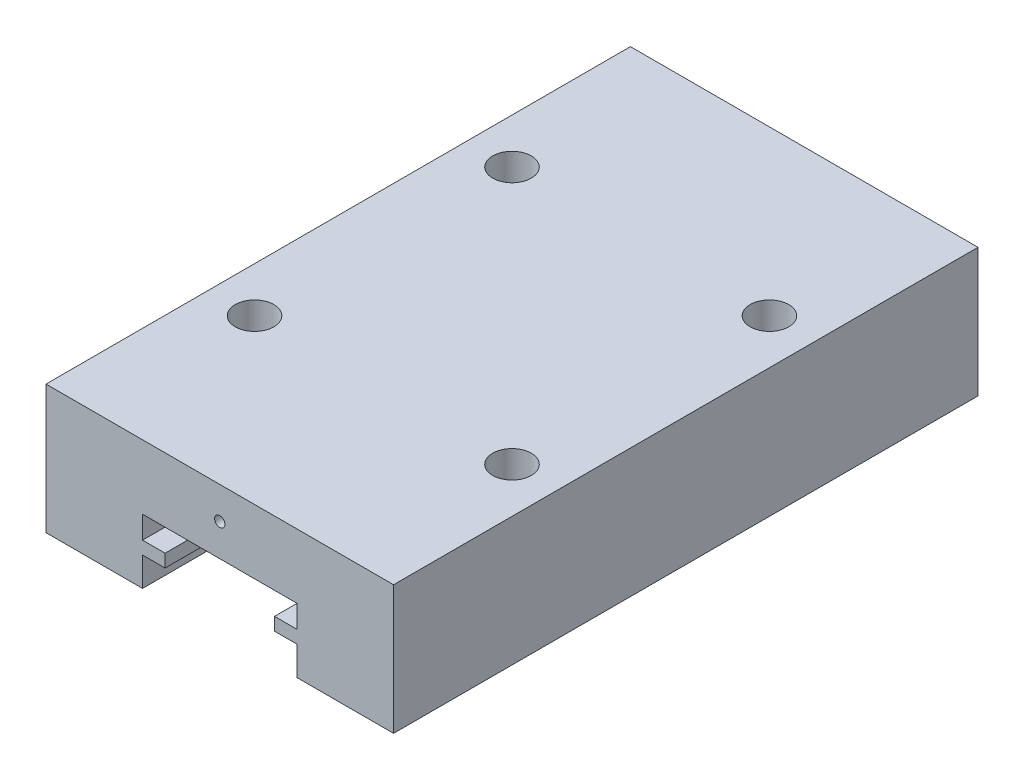
SolidWorks part; units mm, degrees
ref_plane "Płaszczyzna przednia" through (0, 0, 0) normal (0, 0, 1) x (1, 0, 0)
ref_plane "Płaszczyzna górna" through (0, 0, 0) normal (0, 1, 0) x (1, 0, 0)
ref_plane "Płaszczyzna prawa" through (0, 0, 0) normal (1, 0, 0) x (0, 0, -1)
sketch "Szkic1" plane through (0, 0, 0) normal (0, 0, 1) x (1, 0, 0)
  line L0 (7.5, 0) -> (7.5, 2.2479)
  line L1 (0, 0) -> (7.5, 0)
  line L2 (0, 0) -> (0, 10)
  line L3 (0, 10) -> (27, 10)
  line L4 (27, 0) -> (27, 10)
  line L5 (7.5, 2.2479) -> (9.25, 2.2479)
  line L6 (9.25, 2.2479) -> (9.25, 3.2479)
  line L7 (9.25, 3.2479) -> (7.5, 3.2479)
  line L8 (7.5, 3.2479) -> (7.5, 4.9979)
  line L9 (7.5, 4.9979) -> (19.5, 4.9979)
  line L10 (19.5, 4.9979) -> (19.5, 3.2479)
  line L11 (19.5, 3.2479) -> (17.75, 3.2479)
  line L12 (17.75, 3.2479) -> (17.75, 2.2479)
  line L13 (17.75, 2.2479) -> (19.5, 2.2479)
  line L14 (19.5, 2.2479) -> (19.5, 0)
  line L15 (19.5, 0) -> (27, 0)
  dimension "D1" = 27
  dimension "D2" = 10
  dimension "D3" = 7.5
  dimension "D4" = 7.5
  dimension "D5" = 5.0021
  dimension "D6" = 1.75
  dimension "D7" = 1.75
  dimension "D8" = 1
  dimension "D9" = 1.75
  dimension "D10" = 1.75
  dimension "D11" = 1
extrude "Dodanie-wyciągnięcie1" add sketch "Szkic1" along normal blind 45.4
hole_wizard "Otwory ustalające Ø1.0mm1" positions "Szkic3" profile "Szkic4" hole size "Ø1.0" standard "Ansi Metric"
sketch "Szkic3" plane through (0, 0, 45.4) normal (0, 0, 1) x (1, 0, 0)
  line L0 (27, 10) -> (0, 10) construction
  line L1 (27, 0) -> (27, 10) construction
  point P0 (13.5, 7.5)
  dimension "D1" = 2.5
  dimension "D2" = 13.5
sketch "Szkic4" plane through (13.5, 7.5, 45.4) normal (1, 0, 0) x (0, -1, 0)
  line L0 (0, 0) -> (0, 6.7403)
  line L1 (0, 6.7403) -> (0.4, 6.5)
  line L2 (0.4, 6.5) -> (0.4, 0)
  line L5 (0.4, 0) -> (0, 0)
  line L10 (0, 6.7403) -> (-0.4, 6.5) construction
  line L11 (0, -6.35) -> (0, 107.95) construction
  dimension "Œrednica otworu" = 0.8
  dimension "G³êbokoœæ otworu" = 6.5
  dimension "K¹t wiert³a" = 118
hole_wizard "Otwory ustalające Ø1.0mm2" positions "Szkic5" profile "Szkic6" hole size "Ø1.0" standard "Ansi Metric"
sketch "Szkic5" plane through (0, 0, 0) normal (0, 0, -1) x (-1, 0, 0)
  line L0 (-27, 10) -> (0, 10) construction
  line L1 (0, 10) -> (0, 0) construction
  point P0 (-13.5, 7.5)
  dimension "D1" = 2.5
  dimension "D2" = 13.5
sketch "Szkic6" plane through (13.5, 7.5, 0) normal (1, 0, 0) x (0, 1, 0)
  line L0 (0, 0) -> (0, 6.7403)
  line L1 (0, 6.7403) -> (0.4, 6.5)
  line L2 (0.4, 6.5) -> (0.4, 0)
  line L5 (0.4, 0) -> (0, 0)
  line L10 (0, 6.7403) -> (-0.4, 6.5) construction
  line L11 (0, -6.35) -> (0, 107.95) construction
  dimension "Œrednica otworu" = 0.8
  dimension "G³êbokoœæ otworu" = 6.5
  dimension "K¹t wiert³a" = 118
hole_wizard "Otwory ustalające Ø3.0mm1" positions "Szkic7" profile "Szkic8" hole size "Ø3.0" standard "Ansi Metric"
sketch "Szkic7" plane through (0, 10, 0) normal (0, 1, 0) x (1, 0, 0)
  line L0 (27, -45.4) -> (0, -45.4) construction
  line L1 (0, -45.4) -> (0, 0) construction
  point P0 (3.5, -32.7)
  point P13 (23.5, -32.7)
  point P14 (23.5, -12.7)
  point P15 (3.5, -12.7)
  dimension "D1" = 12.7
  dimension "D2" = 3.5
  dimension "D3" = 2
  dimension "D4" = 2
sketch "Szkic8" plane through (3.5, 10, 32.7) normal (1, 0, 0) x (0, 0, 1)
  line L0 (0, 0) -> (0, 4.4013)
  line L1 (0, 4.4013) -> (1.5, 3.5)
  line L2 (1.5, 3.5) -> (1.5, 0)
  line L5 (1.5, 0) -> (0, 0)
  line L10 (0, 4.4013) -> (-1.5, 3.5) construction
  line L11 (0, -6.35) -> (0, 107.95) construction
  dimension "Œrednica otworu" = 3
  dimension "G³êbokoœæ otworu" = 3.5
  dimension "K¹t wiert³a" = 118
